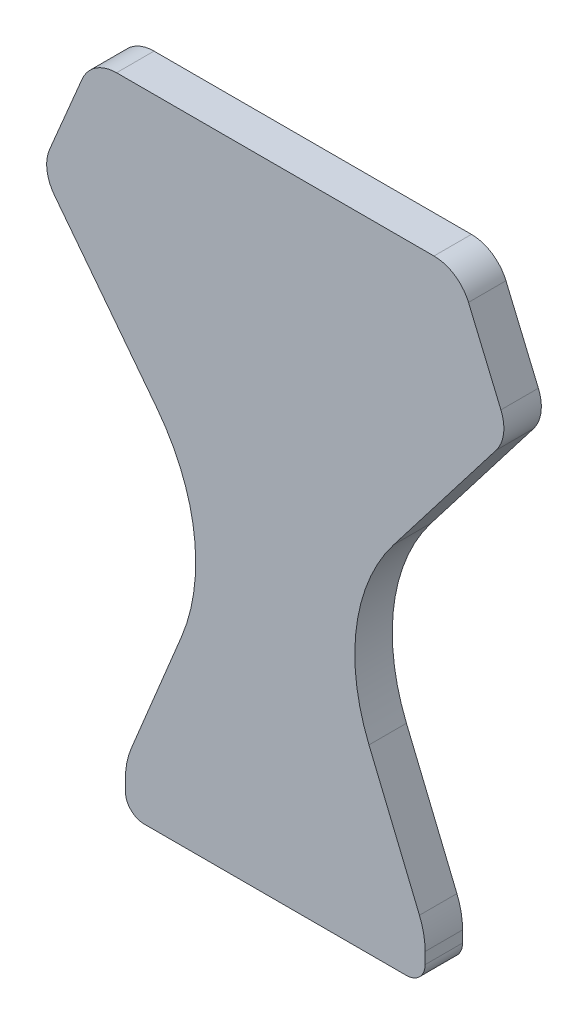
SolidWorks part; units mm, degrees
ref_plane "前视基准面" through (0, 0, 0) normal (0, 0, 1) x (1, 0, 0)
ref_plane "上视基准面" through (0, 0, 0) normal (0, 1, 0) x (1, 0, 0)
ref_plane "右视基准面" through (0, 0, 0) normal (1, 0, 0) x (0, 0, -1)
sketch "草图1" plane through (0, 0, 0) normal (0, 0, 1) x (1, 0, 0)
  line L0 (0, 51.7676) -> (0, -29.4802) construction
  line L1 (0, -5.5) -> (0, 5.5) construction
  line L2 (-49, 139.3874) -> (49, 139.3874)
  line L3 (49, 139.3874) -> (62.5, 107.3874)
  line L4 (62.5, 107.3874) -> (14, 44.3874)
  line L6 (40, -30.6126) -> (-40, -30.6126)
  line L8 (-14, 44.3874) -> (-62.5, 107.3874)
  line L9 (-62.5, 107.3874) -> (-49, 139.3874)
  line L10 (-40, -18.6126) -> (-40, -30.6126)
  line L11 (-40, -18.6126) -> (-14, 44.3874)
  line L12 (14, 44.3874) -> (40, -18.6126)
  line L13 (40, -18.6126) -> (40, -30.6126)
  point P14 (0, 0)
  dimension "D1" = 80
  dimension "D2" = 170
  dimension "D3" = 75
  dimension "D4" = 98
  dimension "D5" = 125
  dimension "D6" = 28
  dimension "D7" = 32
  dimension "D8" = 12
extrude "凸台-拉伸1" add sketch "草图1" along normal blind 10
fillet "圆角4" radius 50 2 edges at (14, 44.3874, 5) (-14, 44.3874, 5)
fillet "圆角2" radius 10 4 edges at (-49, 139.3874, 5) (49, 139.3874, 5) (62.5, 107.3874, 5) (-62.5, 107.3874, 5)
fillet "圆角3" radius 5 2 edges at (40, -30.6126, 5) (-40, -30.6126, 5)
fillet "圆角5" radius 20 2 edges at (40, -18.6126, 5) (-40, -18.6126, 5)
